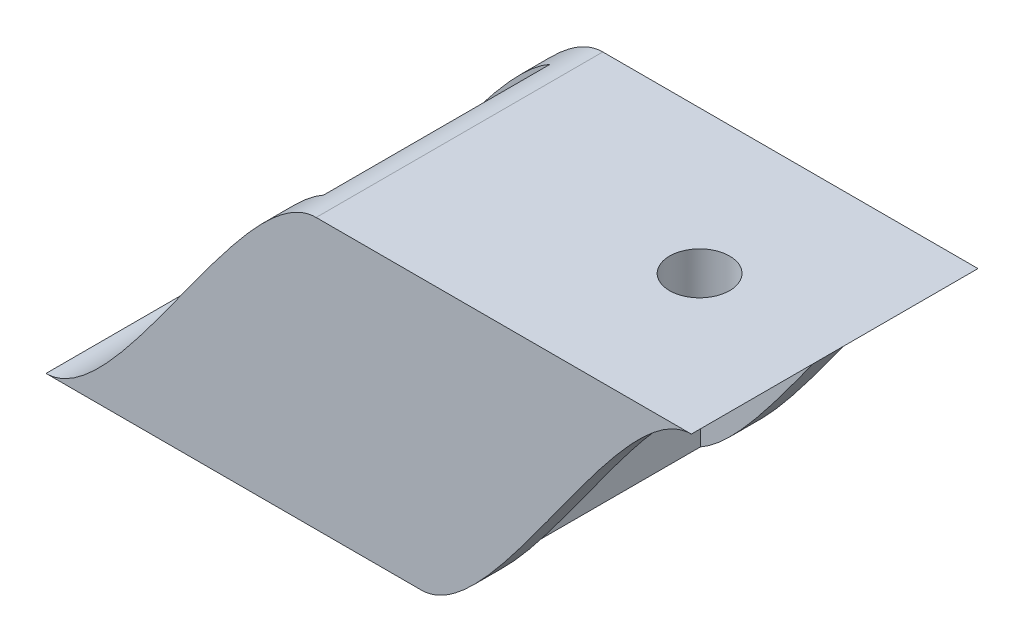
SolidWorks part; units mm, degrees
ref_plane "Front Plane" through (0, 0, 0) normal (0, 0, 1) x (1, 0, 0)
ref_plane "Top Plane" through (0, 0, 0) normal (0, 1, 0) x (1, 0, 0)
ref_plane "Right Plane" through (0, 0, 0) normal (1, 0, 0) x (0, 0, -1)
sketch "Sketch1" plane through (0, 0, 0) normal (0, 0, 1) x (1, 0, 0)
  line L0 (0, 0) -> (36, 36) construction
  line L1 (0, 0) -> (86, 0)
  line L2 (0, 0) -> (0, 36)
  line L3 (0, 36) -> (86, 36)
  line L4 (86, 0) -> (86, 36)
  line L5 (86, 36) -> (50, 0) construction
  dimension "D1" = 36
  dimension "D2" = 86
  dimension "D3" = 45
  dimension "D4" = 45
extrude "Boss-Extrude1" add sketch "Sketch1" along normal blind 38.2 contours L2 L3 L4 L1
sketch "Sketch2" plane through (0, 0, 0) normal (0, 0, 1) x (1, 0, 0)
  line L2 (0, 36) -> (86, 36) construction
  line L3 (43, 0) -> (43, 36) construction
  line L4 (0, 0) -> (86, 0) construction
  line L5 (0, 18) -> (86, 18) construction
  line L6 (0, 0) -> (0, 36) construction
  line L7 (86, 0) -> (86, 36) construction
  line L8 (36, 36) -> (36, 0) construction
  line L10 (0, 0) -> (86, 0) construction
  line L11 (50, 0) -> (50, 36) construction
  line L12 (0, 36) -> (86, 36) construction
  line L16 (36, 36) -> (26, 36) construction
  line L19 (26, 36) -> (10, 0) construction
  line L20 (10, 0) -> (0, 0) construction
  line L21 (50, 0) -> (60, 0) construction
  line L23 (60, 0) -> (76, 36) construction
  line L24 (76, 36) -> (86, 36) construction
  line L25 (86, 36) -> (86, 0)
  line L27 (86, 0) -> (50, 0)
  line L28 (36, 36) -> (0, 36)
  line L29 (0, 36) -> (0, 0)
  spline S0 degree 3 poles (36, 36) (26, 36) (10, 0) (0, 0) knots 0 0 0 0 1 1 1 1
  spline S1 degree 3 poles (50, 0) (60, 0) (76, 36) (86, 36) knots 0 0 0 0 1 1 1 1
  dimension "D2" = 10
  dimension "D3" = 10
  dimension "10" = 10
  dimension "D4" = 10
extrude "Cut-Extrude2" cut sketch "Sketch2" along normal through all contours L28 L29 S0 | S1 L25 L27
sketch "Sketch3" plane through (0, 0, 0) normal (0, 1, 0) x (1, 0, 0)
  line L0 (0, -19.1) -> (36, -19.1) construction
  line L3 (0, -38.2) -> (0, 0) construction
  line L4 (36, -38.2) -> (36, 0) construction
  line L5 (50, -19.1) -> (86, -19.1) construction
  line L6 (50, -38.2) -> (50, 0) construction
  line L7 (86, -38.2) -> (86, 0) construction
  circle A0 centre (18, -19.1) radius 4
  circle A1 centre (18, -19.1) radius 6
  circle A2 centre (68, -19.1) radius 4
  circle A3 centre (68, -19.1) radius 6
  dimension "D1" = 8
  dimension "D2" = 12
  dimension "D3" = 8
  dimension "D4" = 12
extrude "Cut-Extrude5" cut sketch "Sketch3" along normal through all contours A0
extrude "Cut-Extrude7" cut sketch "Sketch3<9>" along normal through all contours A2
sketch "Sketch3<9>" plane through (0, 0, 0) normal (0, 1, 0) x (1, 0, 0) same geometry as "Sketch3"
sketch "Sketch6" plane through (0, 36, 0) normal (0, 1, 0) x (1, 0, 0)
  line L0 (43, -38.2) -> (43, 0) construction
  line L1 (0, -4) -> (33, -4)
  line L2 (0, -4) -> (0, -34.2)
  line L3 (0, -34.2) -> (33, -34.2)
  line L4 (0, 0) -> (86, 0)
  line L5 (0, 0) -> (0, -38.2)
  line L6 (0, -38.2) -> (86, -38.2)
  line L7 (86, 0) -> (86, -38.2)
  line L12 (33, -4) -> (33, -34.2)
  line L14 (86, -4) -> (53, -4)
  line L15 (86, -4) -> (86, -34.2)
  line L16 (86, -34.2) -> (53, -34.2)
  line L17 (53, -4) -> (53, -34.2)
  line L18 (69.5, -34.2) -> (69.5, -4) construction
  line L19 (86, -19.1) -> (53, -19.1) construction
  point P392 (69.5, -19.1)
  dimension "D2" = 4
  dimension "D1" = 10
  dimension "D3" = 4
  dimension "D4" = 10
  dimension "D5" = 4
  dimension "D6" = 4
extrude "Cut-Extrude8" cut sketch "Sketch6" against normal blind 32.2 contours L12 L1 L2 L3 region at (16.5, 36, 19.1)
extrude "Cut-Extrude9" cut sketch "Sketch6<8>" against normal through all from offset 6 contours L16 L17 L14 L15 offset against normal yes
sketch "Sketch6<8>" plane through (0, 36, 0) normal (0, 1, 0) x (1, 0, 0) same geometry as "Sketch6"
